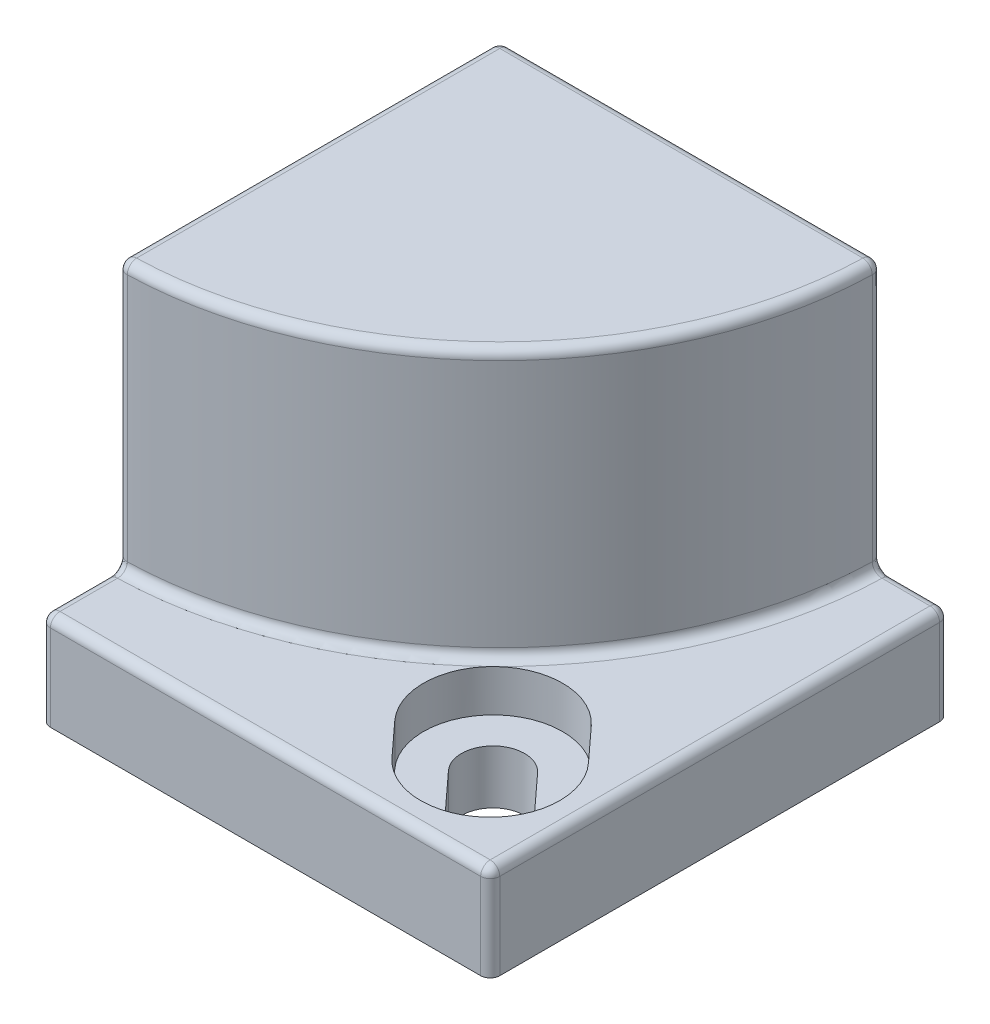
SolidWorks part; units mm, degrees
other "Markup1"
sketch "Sketch1" plane through (0, 0, 0) normal (0.5774, 0.5773, 0.5774) x (0.7071, 0, -0.7071)
sketch "Sketch2" plane through (0, 0, 0) normal (0.5774, 0.5773, 0.5774) x (0.7071, 0, -0.7071)
ref_plane "Front (z)" through (0, 0, 0) normal (0, 0, 1) x (1, 0, 0)
ref_plane "Top (y)" through (0, 0, 0) normal (0, 1, 0) x (1, 0, 0)
ref_plane "Right (x)" through (0, 0, 0) normal (1, 0, 0) x (0, 0, -1)
sketch "Sketch3" plane through (0, 0, 0) normal (0, 1, 0) x (1, 0, 0)
  line L1 (-23.5, -24) -> (23.5, -24)
  line L2 (-23.5, -24) -> (-23.5, 24)
  line L3 (-23.5, 24) -> (23.5, 24)
  line L4 (23.5, -24) -> (23.5, 24)
  line L5 (-23.5, -24) -> (23.5, 24) construction
  line L6 (-23.5, 24) -> (23.5, -24) construction
  point P0 (0, 0)
  dimension "D1" = 47
  dimension "D2" = 48
extrude "Boss-Extrude1" add sketch "Sketch3" along normal blind 10
hole_wizard "CBORE for M6 Hex Head Bolt1" positions "Sketch4" profile "Sketch5" counterbore size "M6" standard "ANSI Metric" end condition through all
sketch "Sketch4" plane through (0, 10, 0) normal (0, 1, 0) x (1, 0, 0)
  line L0 (-23.5, -24) -> (23.5, -24) construction
  line L1 (23.5, -24) -> (23.5, 24) construction
  point P0 (13.5, -14)
  dimension "D1" = 10
  dimension "D2" = 10
sketch "Sketch5" plane through (13.5, 10, 14) normal (1, 0, 0) x (0, 0, 1)
  line L0 (0, 0) -> (0, 10)
  line L1 (0, 10) -> (3.3, 10)
  line L3 (3.3, 10) -> (3.3, 4.38)
  line L4 (3.3, 4.38) -> (7.275, 4.38)
  line L5 (7.275, 4.38) -> (7.275, 0)
  line L7 (7.275, 0) -> (0, 0)
  line L11 (0, -6.35) -> (0, 107.95) construction
  dimension "Thru Hole Dia." = 6.6
  dimension "Thru Hole Depth" = 10
  dimension "C'Bore Dia." = 14.55
  dimension "C'Bore Depth" = 4.38
sketch "Sketch8" plane through (0, 10, 0) normal (0, 1, 0) x (1, 0, 0)
  line L0 (16.5, 24) -> (6.5, 24)
  line L1 (-23.5, -6) -> (-23.5, -16)
  arc A0 (-23.5, -6) -> (6.5, 24) centre (-23.5, 24) ccw
  arc A1 (-23.5, -16) -> (16.5, 24) centre (-23.5, 24) ccw
  circle A3 centre (-23.5, 24) radius 40 construction
  circle A4 centre (-23.5, 24) radius 30 construction
  point P4 (3.6891, 33.7712)
  point P9 (-5, 25)
  dimension "D1" = 60
  dimension "D2" = 10
extrude "Boss-Extrude3" add sketch "Sketch8" along normal blind 18
sketch "Sketch9" plane through (0, 28, 0) normal (0, 1, 0) x (1, 0, 0)
  line L0 (16.5, 24) -> (-23.5, 24)
  line L1 (-23.5, 24) -> (-23.5, -16)
  arc A0 (-23.5, -16) -> (16.5, 24) centre (-23.5, 24) ccw construction
  arc A1 (-23.5, -16) -> (16.5, 24) centre (-23.5, 24) ccw
extrude "Boss-Extrude4" add sketch "Sketch9" along normal blind 10
sketch "Sketch10" plane through (0, 10, 0) normal (0, 1, 0) x (1, 0, 0)
  line L0 (6.5, 24) -> (-23.5, 24) construction
  line L1 (-23.5, 24) -> (-23.5, -6) construction
  circle A0 centre (-11, 11.5) radius 3
  dimension "D1" = 6
  dimension "D2" = 12.5
  dimension "D3" = 12.5
extrude "Cut-Extrude2" cut sketch "Sketch10" against normal blind 6
fillet "Fillet1" radius 1 19 edges at (-8.5, 28, -24) (-8.5, 10, -24) (-23.5, 28, -9) (-23.5, 10, -9) (-23.5, 10, 20) (20, 10, -24) (6.5, 19, -24) (-2.2868, 28, -2.7868) (-23.5, 19, 6) (-2.2868, 10, -2.7868) (-3.5, 38, -24) (-23.5, 38, -4) (-23.5, 24, 16) (4.7843, 38, 4.2843) (16.5, 24, -24) (4.7843, 10, 4.2843) (-23.5, 33, -24) (23.5, 10, 0) (0, 10, 24)
sketch "Sketch11" plane through (0, 10, 0) normal (0, 1, 0) x (1, 0, 0)
  line L0 (23.5, -24) -> (-21.5, 22) construction
  line L1 (4.9171, -15.4019) -> (8.1364, -18.9151)
  line L2 (18.8636, -9.0849) -> (15.6442, -5.5718)
  arc A0 (15.6442, -5.5718) -> (4.9171, -15.4019) centre (10.2806, -10.4869) ccw
  circle A3 centre (13.5, -14) radius 7.275 construction
  arc A4 (8.1364, -18.9151) -> (18.8636, -9.0849) centre (13.5, -14) ccw
  arc A5 (-22.5, -16.9878) -> (17.4878, 23) centre (-23.5, 24) ccw construction
  point P5 (-21.5, 22)
  dimension "D1" = 46
  dimension "D2" = 45
extrude "Cut-Extrude3" cut sketch "Sketch11" against normal up to surface (4.38 mm away) up to face at (13.5, 5.62, 17.3)
sketch "Sketch12" plane through (0, 5.62, 0) normal (0, 1, 0) x (1, 0, 0)
  line L0 (4.9171, -15.4019) -> (15.6442, -5.5718) construction
  line L1 (7.8477, -12.7164) -> (11.067, -16.2295)
  line L2 (12.7136, -8.2574) -> (15.933, -11.7705)
  arc A0 (12.7136, -8.2574) -> (7.8477, -12.7164) centre (10.2806, -10.4869) ccw
  circle A1 centre (13.5, -14) radius 3.3 construction
  arc A2 (11.067, -16.2295) -> (15.933, -11.7705) centre (13.5, -14) ccw
extrude "Cut-Extrude4" cut sketch "Sketch12" against normal through all
fillet "Fillet2" radius 1 8 edges at (-23.2071, 9.7071, 23.7071) (-23.2071, 9.7071, -23.7071) (23.2071, 9.7071, -23.7071) (23.2071, 9.7071, 23.7071) (-23.5, 4.5, 24) (-23.5, 4.5, -24) (23.5, 4.5, -24) (23.5, 4.5, 24)
